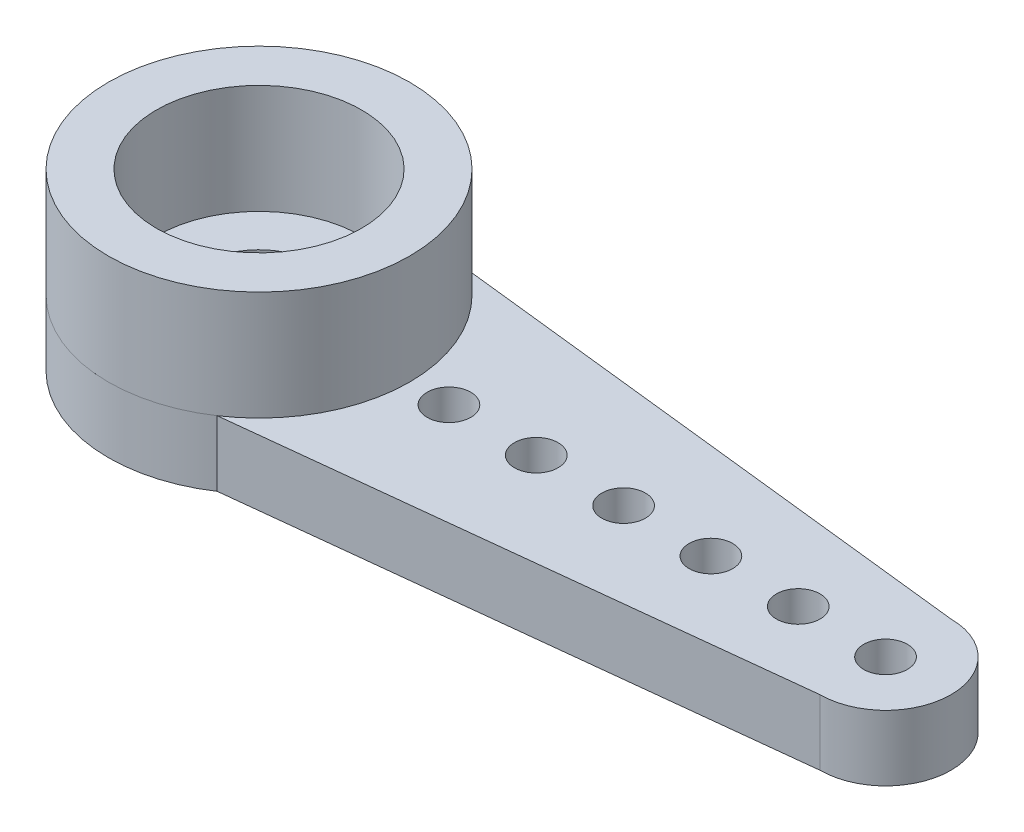
SolidWorks part; units mm, degrees
ref_plane "Front Plane" through (0, 0, 0) normal (0, 0, 1) x (1, 0, 0)
ref_plane "Top Plane" through (0, 0, 0) normal (0, 1, 0) x (1, 0, 0)
ref_plane "Right Plane" through (0, 0, 0) normal (1, 0, 0) x (0, 0, -1)
sketch "Sketch1" plane through (0, 0, 0) normal (0, 1, 0) x (1, 0, 0)
  line L0 (0, 0) -> (15.85, 0) construction
  line L1 (14.35, 1.5) -> (1.8797, 2.8929)
  line L3 (1.9132, -2.8709) -> (14.35, -1.5)
  arc A0 (1.8797, 2.8929) -> (1.9132, -2.8709) centre (0, 0) ccw
  circle A1 centre (0, 0) radius 1.275 construction
  circle A2 centre (0, 0) radius 2.35
  circle A4 centre (12.35, 0) radius 0.5
  circle A5 centre (14.35, 0) radius 0.5
  circle A6 centre (10.35, 0) radius 0.5
  circle A7 centre (8.35, 0) radius 0.5
  circle A9 centre (6.35, 0) radius 0.5
  circle A10 centre (4.35, 0) radius 0.5
  arc A11 (14.35, -1.5) -> (14.35, 1.5) centre (14.35, 0) ccw
  dimension "D1" = 14.35
  dimension "D2" = 2.55
  dimension "D3" = 4.7
  dimension "D4" = 6.9
sketch3d "3DSketch2" plane through (0, 0, 0) normal (0, 0, 1) x (1, 0, 0)
  dimension "D1" = 1.5
extrude "Boss-Extrude1" add sketch "Sketch1" along normal blind 1.5
sketch "Sketch2" plane through (0, 1.5, 0) normal (0, 1, 0) x (1, 0, 0)
  circle A0 centre (0, 0) radius 1.275
  circle A1 centre (0, 0) radius 2.35
  circle A2 centre (0, 0) radius 3.45
extrude "Boss-Extrude3" add sketch "Sketch2" against normal blind 0.5 separate body contours A1 A0 region at (-2.2835, 1.5, 0)
extrude "Boss-Extrude5" add sketch "Sketch2<7>" along normal blind 2.5 separate body contours A2 A1 region at (-3.3524, 1.5, 0)
sketch "Sketch2<7>" plane through (0, 1.5, 0) normal (0, 1, 0) x (1, 0, 0) same geometry as "Sketch2"
